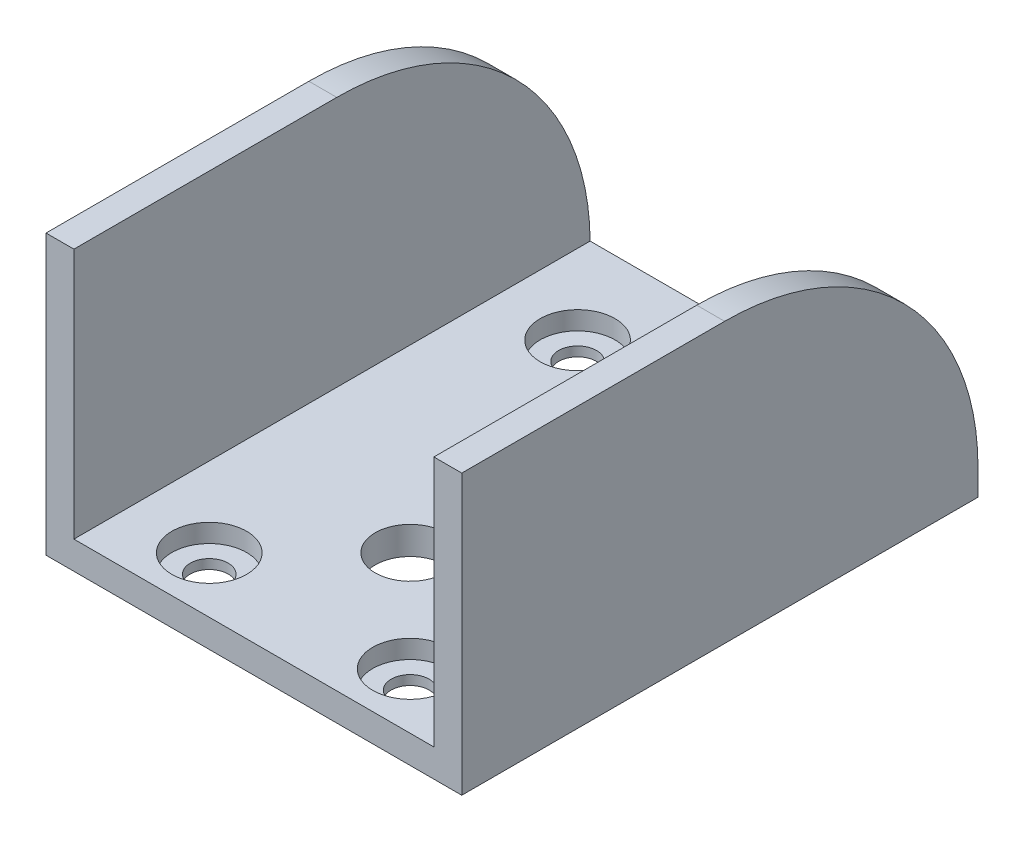
SolidWorks part; units mm, degrees
ref_plane "Front Plane" through (0, 0, 0) normal (0, 0, 1) x (1, 0, 0)
ref_plane "Top Plane" through (0, 0, 0) normal (0, 1, 0) x (1, 0, 0)
ref_plane "Right Plane" through (0, 0, 0) normal (1, 0, 0) x (0, 0, -1)
sketch "Sketch12" plane through (0, 0, 0) normal (0, 1, 0) x (1, 0, 0)
  line L1 (-16.125, -23.125) -> (16.125, -23.125)
  line L2 (-16.125, -23.125) -> (-16.125, 23.125)
  line L3 (-16.125, 23.125) -> (16.125, 23.125)
  line L4 (16.125, -23.125) -> (16.125, 23.125)
  line L5 (-16.125, -23.125) -> (16.125, 23.125) construction
  line L6 (-16.125, 23.125) -> (16.125, -23.125) construction
  point P0 (0, 0)
  dimension "D1" = 32.25
  dimension "D2" = 46.25
extrude "Boss-Extrude2" add sketch "Sketch12" along normal blind 2.5
sketch "Sketch13" plane through (0, 2.5, 0) normal (0, 1, 0) x (1, 0, 0)
  line L0 (0, 23.125) -> (0, -23.125) construction
  line L1 (-9, -18.125) -> (9, -18.125)
  line L2 (-9, -18.125) -> (-9, 14.875)
  line L3 (-9, 14.875) -> (9, 14.875)
  line L4 (9, -18.125) -> (9, 14.875)
  line L5 (-9, -18.125) -> (9, 14.875) construction
  line L6 (-9, 14.875) -> (9, -18.125) construction
  line L7 (16.125, 23.125) -> (-16.125, 23.125) construction
  line L8 (-16.125, -23.125) -> (16.125, -23.125) construction
  point P0 (0, -1.625)
  point P11 (0, -9.125)
  point P12 (0, 0)
  dimension "D1" = 33
  dimension "D2" = 18
  dimension "D3" = 5
  dimension "D4" = 14
hole_wizard "CBORE for M3 SBHCS1" positions "Sketch14" profile "Sketch15" counterbore size "M3" standard "ANSI Metric" end condition through all
sketch "Sketch14" plane through (0, 2.5, 0) normal (0, 1, 0) x (1, 0, 0)
  point P0 (-9, 14.875)
  point P3 (9, 14.875)
  point P6 (9, -18.125)
  point P9 (-9, -18.125)
sketch "Sketch15" plane through (-9, 2.5, -14.875) normal (1, 0, 0) x (0, 0, 1)
  line L0 (0, 0) -> (0, 2.5)
  line L1 (0, 2.5) -> (1.7, 2.5)
  line L3 (1.7, 2.5) -> (1.7, 1.65)
  line L4 (1.7, 1.65) -> (3.35, 1.65)
  line L5 (3.35, 1.65) -> (3.35, 0)
  line L7 (3.35, 0) -> (0, 0)
  line L11 (0, -6.35) -> (0, 107.95) construction
  dimension "Thru Hole Dia." = 3.4
  dimension "Thru Hole Depth" = 2.5
  dimension "C'Bore Dia." = 6.7
  dimension "C'Bore Depth" = 1.65
hole_wizard "Ø6.0mm Dowel Hole1" positions "Sketch18" profile "Sketch19" hole size "Ø6.0" standard "ANSI Metric" end condition through all
sketch "Sketch18" plane through (0, 2.5, 0) normal (0, 1, 0) x (1, 0, 0)
  point P0 (0, -9.125)
sketch "Sketch19" plane through (0, 2.5, 9.125) normal (1, 0, 0) x (0, 0, 1)
  line L0 (0, 0) -> (0, 2.5)
  line L1 (0, 2.5) -> (3.125, 2.5)
  line L2 (3.125, 2.5) -> (3.125, 0)
  line L5 (3.125, 0) -> (0, 0)
  line L11 (0, -6.35) -> (0, 107.95) construction
  dimension "Thru Hole Dia." = 6.25
  dimension "Thru Hole Depth" = 2.5
sketch "Sketch20" plane through (-16.125, 0, 0) normal (-1, 0, 0) x (0, 0, 1)
  line L0 (-23.125, 0) -> (23.125, 0) construction
  line L1 (23.125, 0) -> (-23.125, 0)
  line L2 (23.125, 0) -> (23.125, 25)
  line L3 (23.125, 25) -> (-23.125, 25)
  line L4 (-23.125, 0) -> (-23.125, 25)
  line L5 (-23.125, 2.5) -> (-23.125, 0) construction
  line L6 (23.125, 2.5) -> (23.125, 0) construction
  dimension "D1" = 25
ref_plane "Plane1" through (0, 0, 0) normal (-1, 0, 0) x (0, 0, 1)
extrude "Boss-Extrude3" add sketch "Sketch20" along normal blind 2.5 contours L4 L3 L2 L1
mirror "Mirror1" about plane through (0, 0, 0) normal (-1, 0, 0) of "Boss-Extrude3"
fillet "Fillet1" radius 22.7 1 edges at (-17.375, 25, -23.125)
